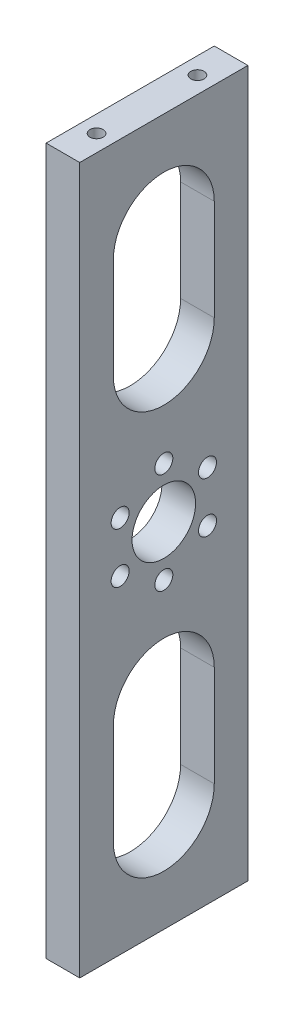
SolidWorks part; units mm, degrees
material "6061 Alloy"
ref_plane "Front Plane" through (0, 0, 0) normal (0, 0, 1) x (1, 0, 0)
ref_plane "Top Plane" through (0, 0, 0) normal (0, 1, 0) x (1, 0, 0)
ref_plane "Right Plane" through (0, 0, 0) normal (1, 0, 0) x (0, 0, -1)
sketch "Sketch1" plane through (0, 0, 0) normal (1, 0, 0) x (0, 0, -1)
  line L1 (-15.875, -66.675) -> (15.875, -66.675)
  line L2 (-15.875, -66.675) -> (-15.875, 66.675)
  line L3 (-15.875, 66.675) -> (15.875, 66.675)
  line L4 (15.875, -66.675) -> (15.875, 66.675)
  line L5 (-15.875, -66.675) -> (15.875, 66.675) construction
  line L6 (-15.875, 66.675) -> (15.875, -66.675) construction
  point P0 (0, 0)
  dimension "D1" = 31.75
  dimension "D2" = 133.35
extrude "Boss-Extrude1" add sketch "Sketch1" along normal mid plane 6.35
sketch "Sketch2" plane through (0, 66.675, 0) normal (0, 1, 0) x (1, 0, 0)
  line L0 (0, 9.525) -> (0, -9.525) construction
  line L1 (-3.175, 15.875) -> (-3.175, -15.875) construction
  line L2 (3.175, 15.875) -> (-3.175, 15.875) construction
  point P2 (0, 0)
  point P5 (-3.175, 0)
  point P8 (0, 15.875)
  point P10 (0, 9.525)
  point P11 (0, -9.525)
  dimension "D1" = 19.05
hole_wizard "M3x0.5 Tapped Hole1" positions "Sketch3" profile "Sketch5" tap size "M3x0.5" standard "ANSI Metric"
sketch "Sketch3" plane through (0, 66.675, 0) normal (0, 1, 0) x (1, 0, 0)
  point P0 (0, 9.525)
  point P3 (0, -9.525)
sketch "Sketch5" plane through (0, 66.675, -9.525) normal (1, 0, 0) x (0, 0, 1)
  line L0 (0, 0) -> (0, 13.4511)
  line L1 (0, 13.4511) -> (1.25, 12.7)
  line L2 (1.25, 12.7) -> (1.25, 0)
  line L5 (1.25, 0) -> (0, 0)
  line L10 (0, 13.4511) -> (-1.25, 12.7) construction
  line L11 (0, -6.35) -> (0, 107.95) construction
  dimension "Tap Drill Dia." = 2.5
  dimension "Tap Drill Depth" = 12.7
  dimension "Drill Angle" = 118
cosmetic thread "Hole Thread1" parameters "D1"=6.096, "D2"=3
cosmetic thread "Hole Thread2" parameters "D1"=6.096, "D2"=3
mirror "Mirror1" about plane through (0, 0, 0) normal (0, 1, 0) of "M3x0.5 Tapped Hole1"
cosmetic thread "Hole Thread3" parameters "D1"=6.096, "D2"=3
cosmetic thread "Hole Thread4" parameters "D1"=6.096, "D2"=3
sketch "Sketch6" plane through (-3.175, 0, 0) normal (-1, 0, 0) x (0, 0, 1)
  point P0 (0, 0)
hole_wizard "Ø12.0mm Dowel Hole1" positions "Sketch7" profile "Sketch8" hole size "Ø12.0" standard "ANSI Metric" end condition through all
sketch "Sketch7" plane through (-3.175, 0, 0) normal (-1, 0, 0) x (0, 0, 1)
  point P0 (0, 0)
sketch "Sketch8" plane through (-3.175, 0, 0) normal (0, 1, 0) x (0, 0, 1)
  line L0 (0, 0) -> (0, 6.35)
  line L1 (0, 6.35) -> (6, 6.35)
  line L2 (6, 6.35) -> (6, 0)
  line L5 (6, 0) -> (0, 0)
  line L11 (0, -6.35) -> (0, 107.95) construction
  dimension "Thru Hole Dia." = 12
  dimension "Thru Hole Depth" = 6.35
sketch "Sketch9" plane through (-3.175, 0, 0) normal (-1, 0, 0) x (0, 0, 1)
  point P0 (0, 9.525)
  point P1 (8.2489, 4.7625)
  point P3 (8.2489, -4.7625)
  point P5 (0, -9.525)
  point P7 (-8.2489, -4.7625)
  point P9 (-8.2489, 4.7625)
hole_wizard "CBORE for M3 SHCS1" positions "Sketch10" profile "Sketch11" counterbore size "M3" standard "ANSI Metric"
sketch "Sketch10" plane through (-3.175, 0, 0) normal (-1, 0, 0) x (0, 0, 1)
  point P0 (8.2489, -4.7625)
  point P3 (8.2489, 4.7625)
  point P6 (0, 9.525)
  point P9 (-8.2489, 4.7625)
  point P12 (-8.2489, -4.7625)
  point P15 (0, -9.525)
sketch "Sketch11" plane through (-3.175, -4.7625, 8.2489) normal (0, 1, 0) x (0, 0, 1)
  line L0 (0, 0) -> (0, 12.7)
  line L1 (0, 12.7) -> (1.7, 11.6785)
  line L2 (1.7, 11.6785) -> (1.7, 2)
  line L3 (1.7, 2) -> (2.25, 2)
  line L4 (2.25, 2) -> (2.25, 0)
  line L5 (2.25, 0) -> (0, 0)
  line L10 (0, 12.7) -> (-1.7, 11.6785) construction
  line L11 (0, -6.35) -> (0, 107.95) construction
  dimension "Hole Dia." = 3.4
  dimension "Hole Depth" = 12.7
  dimension "C'Bore Dia." = 4.5
  dimension "C'Bore Depth" = 2
  dimension "Drill Angle" = 118
sketch "Sketch12" plane through (3.175, 0, 0) normal (1, 0, 0) x (0, 0, -1)
  line L0 (0, 47.625) -> (0, 28.575) construction
  line L1 (9.525, 47.625) -> (9.525, 28.575)
  line L2 (-9.525, 47.625) -> (-9.525, 28.575)
  line L3 (0, -28.575) -> (0, -47.625) construction
  line L4 (9.525, -28.575) -> (9.525, -47.625)
  line L5 (-9.525, -28.575) -> (-9.525, -47.625)
  line L6 (0, 38.1) -> (0, -38.1) construction
  line L7 (3.4925, 0) -> (-3.4925, 0) construction
  arc A0 (9.525, 47.625) -> (-9.525, 47.625) centre (0, 47.625) ccw
  arc A1 (-9.525, 28.575) -> (9.525, 28.575) centre (0, 28.575) ccw
  arc A2 (9.525, -28.575) -> (-9.525, -28.575) centre (0, -28.575) ccw
  arc A3 (-9.525, -47.625) -> (9.525, -47.625) centre (0, -47.625) ccw
  point P3 (0, 38.1)
  point P8 (0, -38.1)
  point P17 (0, -33.3606)
  point P20 (0, 0)
  dimension "D1" = 19.05
  dimension "D2" = 76.2
  dimension "D3" = 19.05
extrude "Cut-Extrude1" cut sketch "Sketch12" against normal through all contours L5 A3 L4 A2 | L1 A1 L2 A0 region at (3.175, -38.1, 0)
